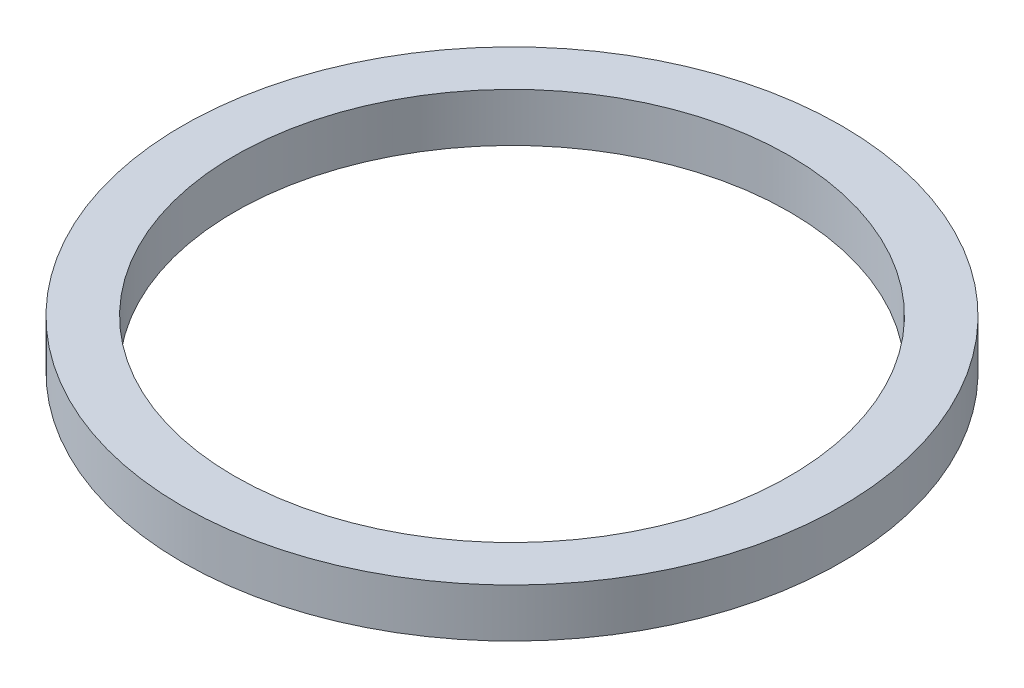
SolidWorks part; units mm, degrees
ref_plane "Front Plane" through (0, 0, 0) normal (0, 0, 1) x (1, 0, 0)
ref_plane "Top Plane" through (0, 0, 0) normal (0, 1, 0) x (1, 0, 0)
ref_plane "Right Plane" through (0, 0, 0) normal (1, 0, 0) x (0, 0, -1)
sketch "Sketch1" plane through (0, 0, 0) normal (0, 1, 0) x (1, 0, 0)
  circle A0 centre (0, 0) radius 47.5
  dimension "FLANGE_OD" = 95
extrude "Boss-Extrude1" add sketch "Sketch1" along normal blind 7
sketch "Sketch2" plane through (0, 0, 0) normal (0, 1, 0) x (1, 0, 0)
  circle A0 centre (0, 0) radius 40
  dimension "BORE_D" = 80
extrude "Cut-Extrude1" cut sketch "Sketch2" along normal through all
sketch "Sketch3" plane through (0, 7, 0) normal (0, 1, 0) x (1, 0, 0)
  circle A0 centre (0, 0) radius 21.5583 construction
  circle A1 centre (-21.5583, 0) radius 1.5
  dimension "BOLT_D" = 3
  dimension "BOLT_PCD" = 43.1165
extrude "Cut-Extrude2" cut sketch "Sketch3" against normal blind 5.932 rebuild error yes
pattern_circular "CirPattern1" count 3 over 360 rebuild error yes
